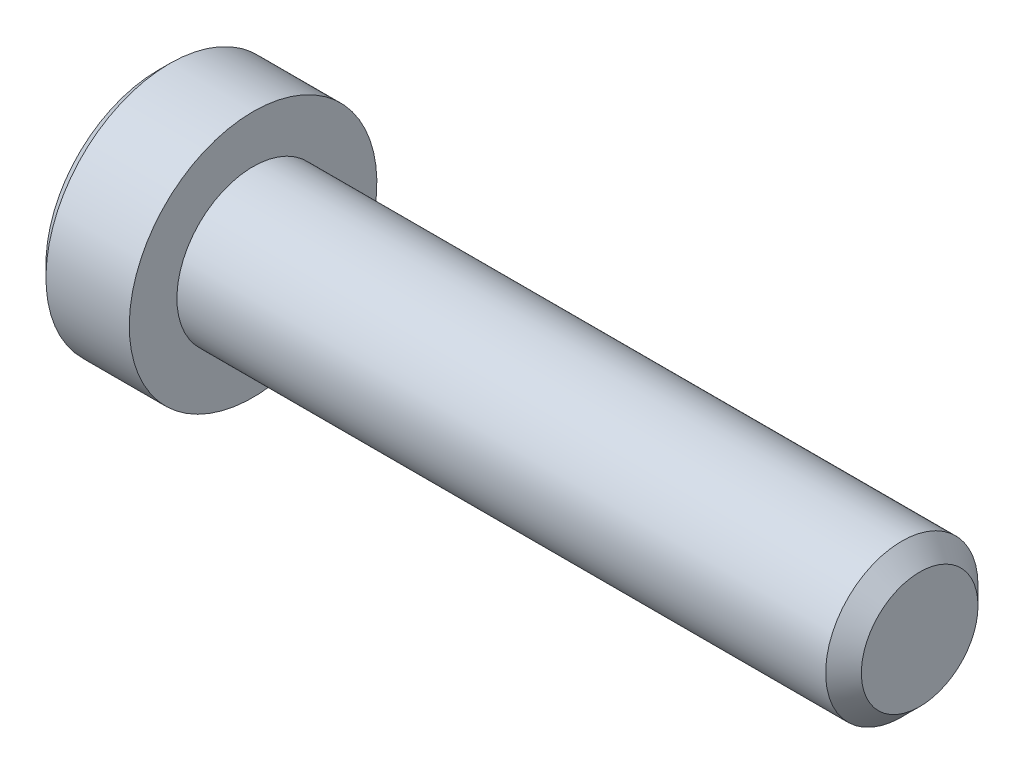
SolidWorks part; units mm, degrees
material "Alloy Steel"
ref_plane "Front Plane" through (0, 0, 0) normal (0, 0, 1) x (1, 0, 0)
ref_plane "Top Plane" through (0, 0, 0) normal (0, 1, 0) x (1, 0, 0)
ref_plane "Right Plane" through (0, 0, 0) normal (1, 0, 0) x (0, 0, -1)
sketch "Sketch1" plane through (0, 0, 0) normal (0, 0, 1) x (1, 0, 0)
  line L0 (17.5, 0) -> (-17.5, 0) construction
  line L1 (17.5, 4) -> (17.5, -4) construction
  line L2 (-17.5, 6.5) -> (-17.5, -6.5) construction
  line L3 (-17.5, 6.5) -> (-21.875, 6.5) construction
  line L4 (-21.875, 6.5) -> (-22.5, 5.875) construction
  line L5 (-22.5, 5.875) -> (-22.5, -5.875) construction
  line L6 (-22.5, -5.875) -> (-21.875, -6.5) construction
  line L7 (-21.875, -6.5) -> (-17.5, -6.5) construction
  line L8 (-4.5, 4) -> (-4.5, -4) construction
  point P7 (-18.55, 0)
  point P12 (12.5, -4)
  dimension "D1" = 45
  dimension "Dec." = 8
  dimension "Length" = 35
  dimension "Head Dia" = 13
  dimension "Head Height" = 5
  dimension "Hex Depth" = 3.95
  dimension "Chamfer" = 0.625
  dimension "D2" = 5
  dimension "Thread Length" = 22
ref_plane "Plane1" through (17.5, 0, 0) normal (1, 0, 0) x (0, 0, -1)
ref_plane "Plane2" through (-22.5, 0, 0) normal (1, 0, 0) x (0, 0, -1)
sketch "Sketch2" plane through (17.5, 0, 0) normal (1, 0, 0) x (0, 0, -1)
  circle A0 centre (0, 0) radius 4
extrude "Boss-Extrude1" add sketch "Sketch2" against normal up to vertex (22 mm away) up to point (-4.5, 4, 0)
sketch "Sketch3" plane through (17.5, 0, 0) normal (1, 0, 0) x (0, 0, -1)
  circle A0 centre (0, 0) radius 4 construction
  circle A1 centre (0, 0) radius 4
curve "Helix/Spiral1" pitch 1.25 height 23.25 turns 18.6 parameters "Pitch"=1.25
chamfer "Chamfer1" distance 0.9375 angle 45 1 edges at (17.5, 0, -4)
sketch "Sketch5" plane through (0, 0, 0) normal (0, 0, 1) x (1, 0, 0)
  line L0 (16.9531, 4) -> (18.0469, 4)
  line L1 (18.0469, 4) -> (17.5781, 3.1881)
  line L2 (17.5781, 3.1881) -> (17.4219, 3.1881)
  line L3 (17.4219, 3.1881) -> (16.9531, 4)
  line L4 (17.5, 3.1881) -> (17.5, 4) construction
  line L5 (17.1875, 3.5941) -> (17.8125, 3.5941) construction
  dimension "D1" = 60
  dimension "D2" = 0.625
  dimension "D3" = 0.1562
sweep "Cut-Sweep1" [suppressed] cut profiles "Sketch5" path "Helix/Spiral1"
sketch "Sketch4" plane through (-22.5, 0, 0) normal (1, 0, 0) x (0, 0, -1)
  line L0 (-6.5, 0.7937) -> (6.5, 0.7937) construction
  line L1 (0, 2.8868) -> (-2.5, 1.4434)
  line L2 (-2.5, 1.4434) -> (-2.5, -1.4434)
  line L3 (-2.5, -1.4434) -> (0, -2.8868)
  line L4 (0, -2.8868) -> (2.5, -1.4434)
  line L5 (2.5, -1.4434) -> (2.5, 1.4434)
  line L6 (2.5, 1.4434) -> (0, 2.8868)
  line L7 (0, 0) -> (0, 0.7937) construction
  circle A0 centre (0, 0) radius 2.5 construction
  dimension "Hex Size" = 5
  dimension "D1" = 13
  dimension "D2" = 0.7937
sketch "Sketch10" plane through (0, 0, 0) normal (0, 0, 1) x (1, 0, 0)
  line L0 (-17.5, 0) -> (-2.1906, 0) construction
  line L1 (-2.1906, 0) -> (-4.5, 4)
  line L2 (-4.5, 4) -> (-17.5, 4)
  line L3 (-17.5, 4) -> (-17.5, 0)
  line L4 (-17.5, 6.5) -> (-17.5, -6.5) construction
  line L5 (-17.5, 0) -> (-2.1906, 0)
  dimension "D1" = 60
revolve "Revolve2" add sketch "Sketch10" angle 360 about L0
sketch "Sketch6" plane through (0, 0, 0) normal (0, 0, 1) x (1, 0, 0)
  line L0 (-21.875, 6.5) -> (-22.5, 5.875) construction
  line L1 (-17.5, 6.5) -> (-21.875, 6.5) construction
  line L2 (-17.5, 6.5) -> (-17.5, -6.5) construction
  line L3 (-22.5, 5.875) -> (-22.5, -5.875) construction
  line L4 (-21.875, 6.5) -> (-22.5, 5.875)
  line L5 (-17.5, 6.5) -> (-21.875, 6.5)
  line L6 (-17.5, 6.5) -> (-17.5, 0)
  line L7 (-22.5, 5.875) -> (-22.5, 0)
  line L8 (-17.5, 0) -> (-22.5, 0) construction
  line L9 (-17.5, 0) -> (-22.5, 0)
revolve "Revolve1" add sketch "Sketch6" angle 360 about L8
extrude "Cut-Extrude1" cut sketch "Sketch4" along normal up to vertex (3.95 mm away) up to point (-18.55, 0, 0)
sketch "Sketch8" plane through (-22.5, 0, 0) normal (-1, 0, 0) x (0, 0, 1)
  circle A1 centre (0, 0) radius 2.8868
extrude "Cut-Extrude2" cut sketch "Sketch8" against normal through all draft 45
sketch "Sketch11" plane through (0, 2.1651, -1.25) normal (0, -0.866, 0.5) x (1, 0, 0)
  line L3 (-22.1132, 0) -> (-18.55, 0) construction
  line L4 (-18.55, -1.4434) -> (-18.55, 1.4434) construction
  circle A0 centre (-20.3316, 0) radius 0.7937
  spline S0 degree 3 poles (-22.5, -1.4434) (-22.3872, -1.2178) (-22.2913, -0.9872) (-22.1886, -0.6289) (-22.1613, -0.5073) (-22.1236, -0.2591) (-22.1135, -0.1313) (-22.1127, 0.2467) (-22.1509, 0.4944) (-22.2893, 0.9829) (-22.3866, 1.2165) (-22.5, 1.4434) knots 0 0 0 0 0.25 0.25 0.375 0.375 0.5 0.5 0.75 0.75 1 1 1 1 construction
  point P15 (-20.3316, 0)
  dimension "D1" = 1.5875
extrude "Cut-Extrude3" [suppressed] cut sketch "Sketch11" against normal through all both and the other way through all
equation "\"D3@Helix/Spiral1\" = \"Thread Length@Sketch1\"+\"Pitch@Helix/Spiral1\""
equation "\"D3@Sketch5\" = \"Pitch@Helix/Spiral1\"*.125"
equation "\"D2@Sketch5\" = \"Pitch@Helix/Spiral1\"*.50"
equation "\"D1@Chamfer1\" = \"Pitch@Helix/Spiral1\"*.75"
equation "\"D2@Sketch1\" = \"Pitch@Helix/Spiral1\"*4"
equation "\"D1@Sketch4\" = \"Head Dia@Sketch1\""
equation "\"Chamfer@Sketch1\" = \"Head Height@Sketch1\"/8"
